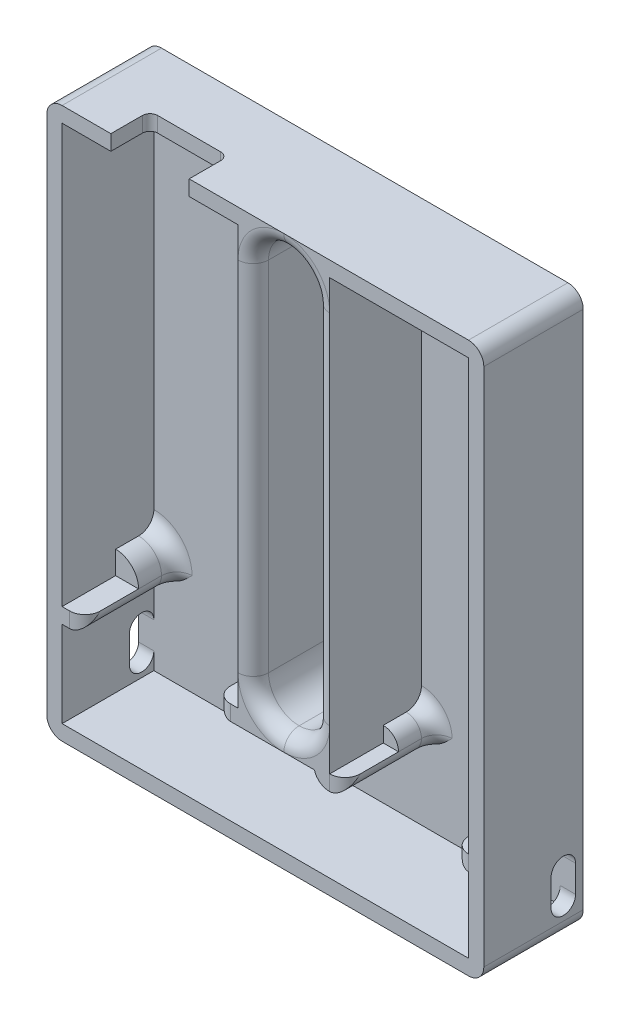
SolidWorks part; units mm, degrees
ref_plane "Front Plane" through (0, 0, 0) normal (0, 0, 1) x (1, 0, 0)
ref_plane "Top Plane" through (0, 0, 0) normal (0, 1, 0) x (1, 0, 0)
ref_plane "Right Plane" through (0, 0, 0) normal (1, 0, 0) x (0, 0, -1)
sketch "Sketch1" plane through (0, 0, 0) normal (0, 0, 1) x (1, 0, 0)
  line L12 (-16.62, -3.82) -> (1.38, -3.82)
  line L13 (1.38, -3.82) -> (1.38, 39.38)
  line L14 (1.38, 39.38) -> (-16.62, 39.38)
  line L15 (-16.62, 39.38) -> (-16.62, -3.82)
  line L16 (-16.62, -3.82) -> (1.38, -3.82) construction
  line L17 (1.38, -3.82) -> (1.38, 39.38) construction
  line L18 (1.38, 39.38) -> (-16.62, 39.38) construction
  line L19 (-16.62, 39.38) -> (-16.62, -3.82) construction
  line L20 (-16.747, 39.507) -> (-16.747, -3.947)
  line L21 (-16.747, -3.947) -> (-14.3658, -3.947)
  line L22 (1.507, -3.947) -> (1.507, 39.507)
  line L23 (1.507, 39.507) -> (-16.747, 39.507)
  line L24 (-18.3345, 41.0945) -> (-18.3345, -5.5345)
  line L25 (-16.747, -5.5345) -> (-14.3658, -5.5345)
  line L26 (3.0945, -3.947) -> (3.0945, 39.507)
  line L27 (3.0945, 41.0945) -> (-18.3345, 41.0945)
  line L28 (25.436, 39.507) -> (11.032, 39.507)
  line L29 (11.032, 39.507) -> (11.032, -5.097)
  line L30 (11.032, -5.097) -> (12.6195, -5.097)
  line L31 (25.436, -5.097) -> (25.436, 39.507)
  line L32 (11.159, 39.38) -> (11.159, -4.97)
  line L33 (11.159, -4.97) -> (25.309, -4.97)
  line L34 (25.309, -4.97) -> (25.309, 39.38)
  line L35 (25.309, 39.38) -> (11.159, 39.38)
  line L36 (11.159, 39.38) -> (11.159, -4.97) construction
  line L37 (11.159, -4.97) -> (25.309, -4.97) construction
  line L38 (25.309, -4.97) -> (25.309, 39.38) construction
  line L39 (25.309, 39.38) -> (11.159, 39.38) construction
  line L40 (9.4445, 39.507) -> (9.4445, -3.947)
  line L41 (9.4445, -6.6845) -> (12.6195, -6.6845)
  line L42 (27.0235, -6.6845) -> (27.0235, 41.0945)
  line L43 (27.0235, 41.0945) -> (9.4445, 41.0945)
  line L44 (3.0945, 39.507) -> (9.4445, 39.507)
  line L45 (9.4445, 41.0945) -> (9.4445, -6.6845) construction
  line L46 (3.0945, -5.5345) -> (3.0945, 41.0945) construction
  line L47 (3.0945, 41.0945) -> (9.4445, 41.0945)
  line L48 (3.0945, -3.947) -> (9.4445, -3.947)
  line L49 (3.0945, -5.5345) -> (9.4445, -5.5345)
  line L50 (9.4445, -5.5345) -> (9.4445, -6.6845)
  line L51 (-18.3345, -5.5345) -> (-18.3345, -16.0555)
  line L52 (-18.3345, -16.0555) -> (27.0235, -16.0555)
  line L53 (27.0235, -16.0555) -> (27.0235, -6.6845)
  line L54 (-16.747, -5.5345) -> (-16.747, -14.468)
  line L55 (-16.747, -14.468) -> (25.436, -14.468)
  line L56 (25.436, -14.468) -> (25.436, -6.6845)
  line L57 (-18.3345, -5.5345) -> (3.0945, -5.5345) construction
  line L58 (27.0235, -16.0555) -> (27.0235, -7.1241) construction
  line L59 (25.436, -14.468) -> (25.436, -7.1241) construction
  line L60 (9.4445, -6.6845) -> (27.0235, -6.6845) construction
  line L61 (-14.3658, -3.947) -> (-14.3658, -5.5345)
  line L62 (-0.8743, -5.5345) -> (-0.8743, -3.947)
  line L63 (12.6195, -6.6845) -> (12.6195, -5.097)
  line L64 (23.8485, -6.6845) -> (23.8485, -5.097)
  line L65 (-0.8743, -5.5345) -> (3.0945, -5.5345)
  line L66 (-0.8743, -3.947) -> (1.507, -3.947)
  line L67 (-16.747, -3.947) -> (1.507, -3.947) construction
  line L68 (23.8485, -6.6845) -> (25.436, -6.6845)
  line L69 (23.8485, -5.097) -> (25.436, -5.097)
  line L70 (11.032, -5.097) -> (25.436, -5.097) construction
  dimension "D1" = 0
  dimension "D2" = 0.127
  dimension "D3" = 1.5875
  dimension "D4" = 0
  dimension "D5" = 0.127
  dimension "D7" = 57.15
  dimension "D9" = 1.5875
  dimension "D10" = 1.5875
  dimension "D11" = 2.3813
  dimension "D12" = 2.3813
  dimension "D6" = 1.5875
  dimension "D8" = 1.5875
extrude "Boss-Extrude1" add sketch "Sketch1" against normal blind 3.9688 and the other way blind 5.5562
sketch "Sketch2" plane through (0, 0, -3.9688) normal (0, 0, -1) x (-1, 0, 0)
  line L4 (-27.0235, 41.0945) -> (-27.0235, -16.0555)
  line L5 (18.3345, 41.0945) -> (-27.0235, 41.0945)
  line L6 (-27.0235, 41.0945) -> (-27.0235, -16.0555)
  line L7 (-27.0235, -16.0555) -> (18.3345, -16.0555)
  line L8 (18.3345, -16.0555) -> (18.3345, 41.0945)
  line L9 (18.3345, 41.0945) -> (-27.0235, 41.0945)
  line L12 (18.3345, -16.0555) -> (18.3345, 41.0945)
  line L13 (-27.0235, -16.0555) -> (18.3345, -16.0555)
  line L14 (-9.4445, 39.507) -> (-9.4445, -3.947)
  line L15 (-3.0945, 39.507) -> (-9.4445, 39.507)
  line L16 (-3.0945, -3.947) -> (-3.0945, 39.507)
  line L17 (-9.4445, -3.947) -> (-3.0945, -3.947)
  line L18 (-9.4445, 39.507) -> (-9.4445, -3.947)
  line L19 (-3.0945, 39.507) -> (-9.4445, 39.507)
  line L20 (-3.0945, -3.947) -> (-3.0945, 39.507)
  line L21 (-9.4445, -3.947) -> (-3.0945, -3.947)
  dimension "D1" = 0
  dimension "D2" = 0
extrude "Boss-Extrude2" add sketch "Sketch2" along normal blind 0.7937
sketch "Sketch3" plane through (0, 41.0945, 0) normal (0, 1, 0) x (1, 0, 0)
  line L0 (27.0235, -5.5562) -> (-18.3345, -5.5562) construction
  line L1 (-3.556, -5.5563) -> (-11.684, -5.5563)
  line L2 (-3.556, -5.5563) -> (-3.556, -1.4922)
  line L3 (-3.556, -1.4922) -> (-11.684, -1.4922)
  line L4 (-11.684, -5.5563) -> (-11.684, -1.4922)
  line L6 (-11.47, -4.1134) -> (-3.77, -4.1134) construction
  line L7 (-3.77, -3.93) -> (-3.77, -4.75) construction
  line L8 (-11.47, -4.75) -> (-11.47, -3.93) construction
  point P9 (-7.62, -1.4922)
  point P10 (0, 0)
  point P17 (0, 0)
  point P18 (-7.62, -4.1134)
  dimension "D1" = 8.128
  dimension "D2" = 4.064
extrude "Cut-Extrude1" cut sketch "Sketch3" against normal up to next
fillet "Fillet1" radius 0.7937 2 edges at (-11.684, 40.3007, 1.4922) (-3.556, 40.3007, 1.4922)
sketch "Sketch4" plane through (0, 0, -3.9688) normal (0, 0, 1) x (1, 0, 0)
  line L0 (-16.747, -3.947) -> (-14.3658, -3.947) construction
  line L1 (-16.747, 39.507) -> (-16.747, -3.947) construction
  line L2 (-16.747, -1.5657) -> (-16.747, -3.947)
  line L3 (-16.747, -3.947) -> (-14.3657, -3.947)
  line L4 (-7.62, -3.947) -> (-7.62, 3.7533) construction
  line L5 (-16.747, 17.78) -> (1.507, 17.78) construction
  line L6 (1.507, -3.947) -> (-0.8742, -3.947)
  line L7 (1.507, -1.5657) -> (1.507, -3.947)
  line L8 (1.507, 37.1258) -> (1.507, 39.507)
  line L9 (1.507, 39.507) -> (-0.8742, 39.507)
  line L10 (-16.747, 39.507) -> (-14.3657, 39.507)
  line L11 (-16.747, 37.1258) -> (-16.747, 39.507)
  line L12 (1.507, -3.947) -> (1.507, 39.507) construction
  line L13 (11.032, 39.507) -> (11.032, -5.097) construction
  line L14 (25.436, -5.097) -> (25.436, 39.507) construction
  line L15 (25.436, 39.507) -> (11.032, 39.507) construction
  line L16 (11.032, 37.9195) -> (11.032, 39.507)
  line L17 (11.032, 39.507) -> (12.6195, 39.507)
  line L18 (23.8485, 39.507) -> (25.436, 39.507)
  line L19 (25.436, 39.507) -> (25.436, 37.9195)
  line L20 (23.8485, -5.097) -> (25.436, -5.097)
  line L21 (25.436, -5.097) -> (25.436, -3.5095)
  line L22 (11.032, -3.5095) -> (11.032, -5.097)
  line L23 (11.032, -5.097) -> (12.6195, -5.097)
  arc A0 (-14.3657, -3.947) -> (-16.747, -1.5657) centre (-16.747, -3.947) ccw
  arc A1 (-0.8742, -3.947) -> (1.507, -1.5657) centre (1.507, -3.947) cw
  arc A2 (-0.8742, 39.507) -> (1.507, 37.1258) centre (1.507, 39.507) ccw
  arc A3 (-14.3657, 39.507) -> (-16.747, 37.1258) centre (-16.747, 39.507) cw
  arc A4 (12.6195, -5.097) -> (11.032, -3.5095) centre (11.032, -5.097) ccw
  arc A5 (23.8485, -5.097) -> (25.436, -3.5095) centre (25.436, -5.097) cw
  arc A6 (23.8485, 39.507) -> (25.436, 37.9195) centre (25.436, 39.507) ccw
  arc A7 (11.032, 37.9195) -> (12.6195, 39.507) centre (11.032, 39.507) ccw
  point P26 (-7.62, 17.78)
  dimension "D1" = 2.3813
extrude "Boss-Extrude3" add sketch "Sketch4" along normal up to surface (3.9688 mm away)
fillet "Fillet2" radius 1.5875 4 edges at (-18.3345, 41.0945, 0.3969) (27.0235, 41.0945, 0.3969) (27.0235, -16.0555, 0.3969) (-18.3345, -16.0555, 0.3969)
fillet "Fillet3" radius 3.175 4 edges at (9.4445, -3.947, 0.3969) (3.0945, -3.947, 0.3969) (9.4445, 39.507, 0.3969) (3.0945, 39.507, 0.3969)
fillet "Fillet4" radius 1.5875 8 edges at (24.3135, -3.9745, -3.9688) (12.1545, -3.9745, -3.9688) (23.8485, -5.8907, -3.9688) (12.6195, -5.8907, -3.9688) (-0.8743, -4.7407, -3.9688) (-14.3658, -4.7408, -3.9688) (-15.0632, -2.2632, -3.9688) (-0.1768, -2.2632, -3.9688)
sketch "Sketch5" plane through (27.0235, 0, 0) normal (1, 0, 0) x (0, 0, -1)
  line L0 (2.6987, -12.69) -> (2.6987, -9.896) construction
  line L1 (1.4287, -12.69) -> (1.4287, -9.896)
  line L2 (3.9688, -12.69) -> (3.9688, -9.896)
  line L3 (3.9688, -5.5345) -> (3.9688, -14.468) construction
  line L4 (4.7625, -16.0555) -> (-5.5562, -16.0555) construction
  arc A0 (1.4287, -12.69) -> (3.9688, -12.69) centre (2.6987, -12.69) ccw
  arc A1 (3.9688, -9.896) -> (1.4287, -9.896) centre (2.6987, -9.896) ccw
  point P2 (2.6987, -11.293)
  point P9 (2.6987, -13.96)
  point P10 (2.6987, -8.626)
  point P11 (2.3813, -9.3575)
  dimension "D1" = 2.54
  dimension "D2" = 5.334
  dimension "D3" = 4.7625
extrude "Cut-Extrude2" cut sketch "Sketch5" against normal through all
fillet "Fillet5" radius 1.5875 11 edges at (4.0244, 38.5771, 5.5562) (8.5146, 38.5771, 5.5562) (9.4445, 17.78, 5.5562) (8.5146, -3.0171, 5.5562) (4.0244, -3.0171, 5.5562) (9.4445, -6.6845, 0.7937) (-0.1768, 37.8232, -3.9688) (-15.0632, 37.8232, -3.9688) (24.3135, 38.3845, -3.9688) (12.1545, 38.3845, -3.9688) (3.0945, 17.78, 5.5562)
fillet "Fillet6" radius 1.5875 12 edges at (23.3835, -6.6845, -3.5038) (13.0845, -6.6845, -3.5038) (-13.9008, -5.5345, -3.5038) (-1.3392, -5.5345, -3.5038) (23.8485, -6.6845, 1.5875) (12.6195, -6.6845, 1.5875) (-14.3658, -5.5345, 1.5875) (-0.8743, -5.5345, 1.5875) (23.8485, -5.8907, 5.5562) (12.6195, -5.8907, 5.5562) (-0.8743, -4.7407, 5.5562) (-14.3658, -4.7408, 5.5562)
